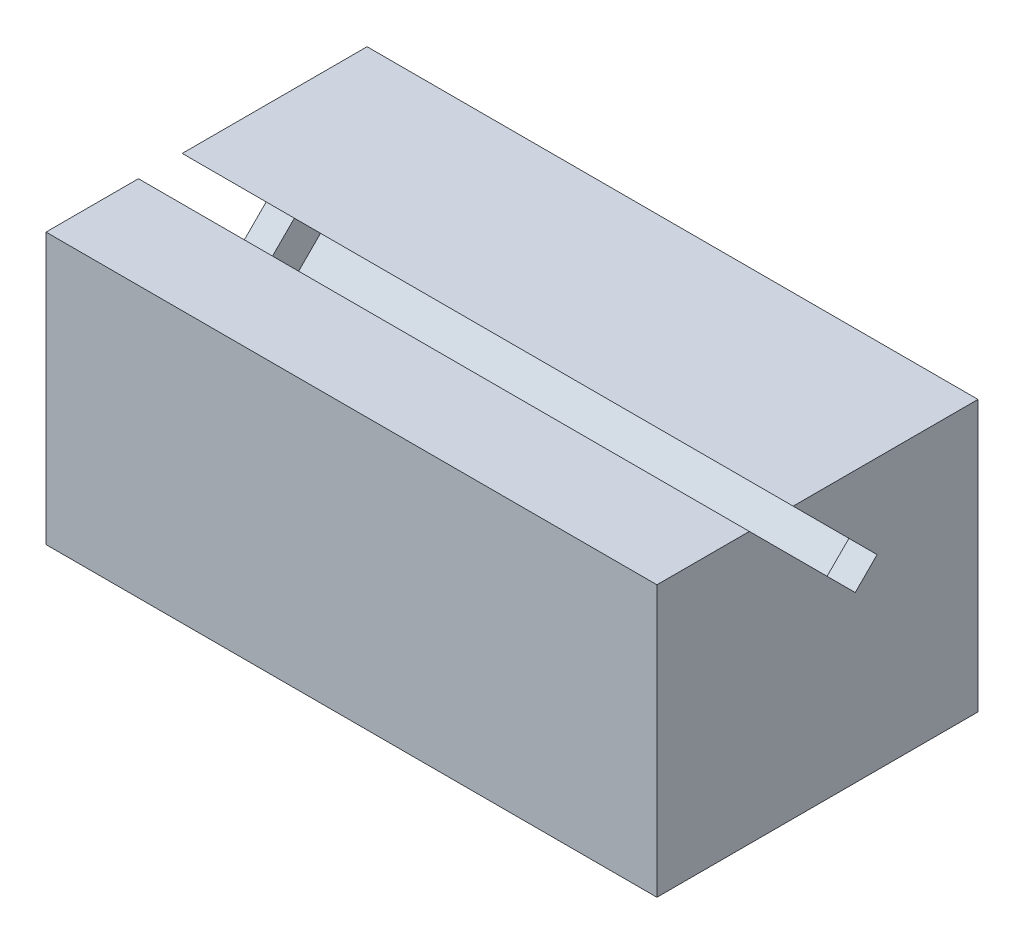
SolidWorks part; units mm, degrees
ref_plane "Front Plane" through (0, 0, 0) normal (0, 0, 1) x (1, 0, 0)
ref_plane "Top Plane" through (0, 0, 0) normal (0, 1, 0) x (1, 0, 0)
ref_plane "Right Plane" through (0, 0, 0) normal (1, 0, 0) x (0, 0, -1)
sketch "Sketch1" plane through (0, 0, 0) normal (1, 0, 0) x (0, 0, -1)
  line L0 (0, 0) -> (0, 29.2836)
  line L1 (0, 29.2836) -> (10, 29.2836)
  line L2 (34.7376, 29.2836) -> (34.7376, 0)
  line L3 (34.7376, 0) -> (0, 0)
  line L4 (10, 29.2836) -> (24.2836, 15)
  line L5 (24.2836, 15) -> (26.6524, 17.3688)
  line L6 (26.6524, 17.3688) -> (14.7376, 29.2836)
  line L7 (23.8239, 20.1972) -> (21.4551, 17.8284)
  line L8 (14.7376, 29.2836) -> (34.7376, 29.2836)
  dimension "D2" = 20.2
  dimension "D3" = 3.35
  dimension "D4" = 10
  dimension "D5" = 20
  dimension "D6" = 15
  dimension "D7" = 4
  dimension "D1" = 45
extrude "Boss-Extrude1" add sketch "Sketch1" along normal blind 66.1 contours L8 L6 L5 L4 L1 L0 L3 L2 region at (0, 14.1172, -17.2716)
extrude "Boss-Extrude2" add sketch "Sketch1<4>" along normal blind 3.05 contours L6 L7 L4 L5 region at (0, 17.5986, -24.0537)
sketch "Sketch1<4>" plane through (0, 0, 0) normal (1, 0, 0) x (0, 0, -1) same geometry as "Sketch1"
ref_plane "Plane1" through (33.05, 0, 0) normal (-1, 0, 0) x (0, 0, 1)
mirror "Mirror1" about plane through (33.05, 0, 0) normal (-1, 0, 0) of "Boss-Extrude2"
equation "\"D2@Sketch1\"=20.05 + 0.15"
equation "\"D3@Sketch1\"=3.20 + 0.15"
